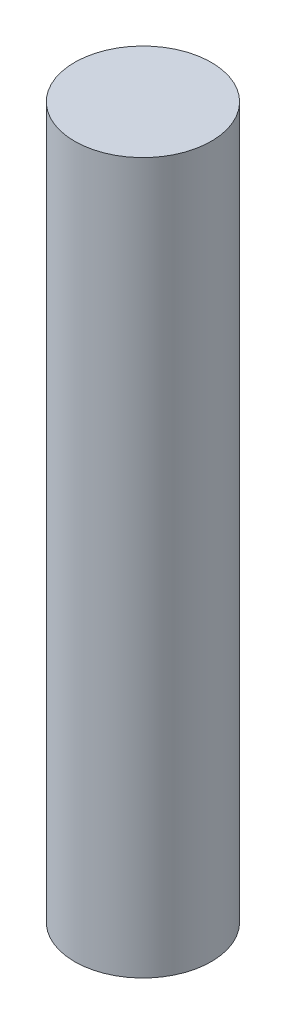
SolidWorks part; units mm, degrees
ref_plane "Plan de face" through (0, 0, 0) normal (0, 0, 1) x (1, 0, 0)
ref_plane "Plan de dessus" through (0, 0, 0) normal (0, 1, 0) x (1, 0, 0)
ref_plane "Plan de droite" through (0, 0, 0) normal (1, 0, 0) x (0, 0, -1)
sketch "Esquisse1" plane through (0, 0, 0) normal (0, 1, 0) x (1, 0, 0)
  circle A0 centre (0, 0) radius 3.175
  dimension "D1" = 6.35
extrude "Boss.-Extru.1" add sketch "Esquisse1" along normal mid plane 33
sketch "Esquisse2" plane through (0, 0, 0) normal (0, 1, 0) x (1, 0, 0)
  point P0 (0, 0)
